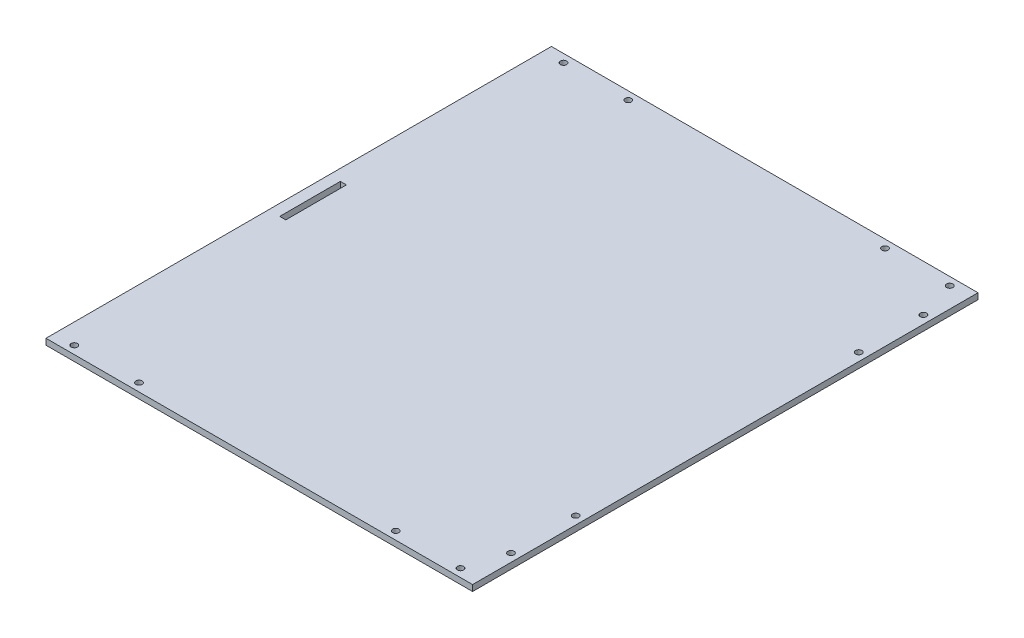
SolidWorks part; units mm, degrees
ref_plane "Front Plane" through (0, 0, 0) normal (0, 0, 1) x (1, 0, 0)
ref_plane "Top Plane" through (0, 0, 0) normal (0, 1, 0) x (1, 0, 0)
ref_plane "Right Plane" through (0, 0, 0) normal (1, 0, 0) x (0, 0, -1)
sketch "Sketch1" plane through (0, 0, 0) normal (0, 1, 0) x (1, 0, 0)
  line L0 (0, 125) -> (211, 125) construction
  line L1 (0, 0) -> (211, 0)
  line L2 (0, 0) -> (0, 250)
  line L3 (0, 250) -> (211, 250)
  line L4 (211, 0) -> (211, 250)
  line L5 (105.5, 250) -> (105.5, 0) construction
  line L6 (7.1, 140) -> (7.1, 110) construction
  line L7 (5.6, 140) -> (8.6, 140)
  line L8 (5.6, 140) -> (5.6, 110)
  line L9 (5.6, 110) -> (8.6, 110)
  line L10 (8.6, 140) -> (8.6, 110)
  circle A0 centre (10, 4) radius 1.55
  circle A4 centre (42, 4) radius 1.55
  circle A5 centre (42, 246) radius 1.55
  circle A6 centre (10, 246) radius 1.55
  circle A7 centre (169, 4) radius 1.55
  circle A8 centre (201, 4) radius 1.55
  circle A9 centre (169, 246) radius 1.55
  circle A10 centre (201, 246) radius 1.55
  circle A11 centre (207, 23) radius 1.55
  circle A12 centre (207, 55) radius 1.55
  circle A13 centre (207, 227) radius 1.55
  circle A14 centre (207, 195) radius 1.55
  point P39 (7.1, 125)
  dimension "D3" = 3.1
  dimension "D8" = 3.1
  dimension "D1" = 250
  dimension "D2" = 211
  dimension "D4" = 4
  dimension "D5" = 10
  dimension "D6" = 32
  dimension "D7" = 23
  dimension "D9" = 4
  dimension "D10" = 32
  dimension "D11" = 7.1
  dimension "D12" = 3
  dimension "D13" = 30
extrude "Boss-Extrude1" add sketch "Sketch1" along normal blind 3
equation "\"cf_tube_outer_diameter\"= 25mm"
equation "\"cf_tube_inner_diameter\"= 21mm"
equation "\"mid_plate_mid_to_top\"= 100mm"
equation "\"mid_plate_mid_to_bottom\"= 30mm"
equation "\"mid_plate_horizontal_spacing\"= 250mm"
equation "\"cf_plate_thickness\"= 3mm"
equation "\"mid_tube_length\"= 500mm"
equation "\"mid_plate_bottom_width\"= 180mm"
equation "\"D1@Sketch1\"=\"mid_plate_horizontal_spacing\""
equation "\"mid_support_plate_distance\"= 250mm"
equation "\"D1@Boss-Extrude1\"=\"cf_plate_thickness\""
equation "\"nut_strip_2_hole_distance\"= 7mm"
equation "\"nut_strip_hole_diameter\"= 2.5mm"
equation "\"nut_strip_hole_to_edge_distance\"= 2.5mm"
equation "\"M3_screw_hole_diameter\"= 3.1mm"
equation "\"D3@Sketch1\"=\"M3_screw_hole_diameter\""
equation "\"D8@Sketch1\"=\"M3_screw_hole_diameter\""
